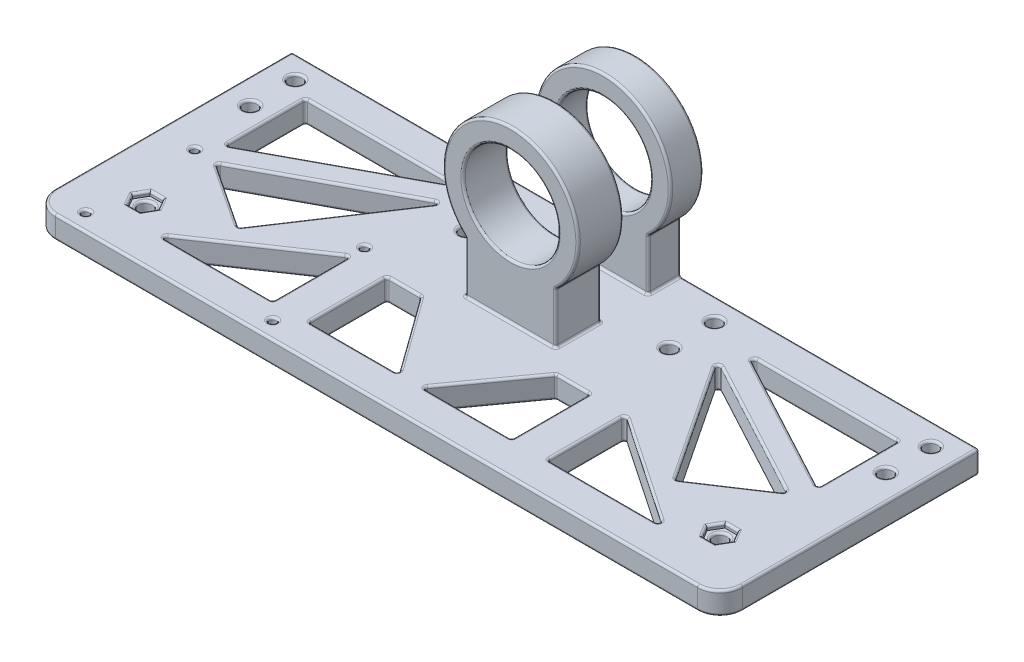
SolidWorks part; units mm, degrees
ref_plane "Front Plane" through (0, 0, 0) normal (0, 0, 1) x (1, 0, 0)
ref_plane "Top Plane" through (0, 0, 0) normal (0, 1, 0) x (1, 0, 0)
ref_plane "Right Plane" through (0, 0, 0) normal (1, 0, 0) x (0, 0, -1)
sketch "Sketch1" plane through (0, 0, 0) normal (0, 1, 0) x (1, 0, 0)
  line L0 (152.5, 115) -> (152.5, 0) construction
  line L1 (0, 0) -> (305, 0)
  line L2 (0, 0) -> (0, 115)
  line L3 (0, 115) -> (305, 115)
  line L4 (305, 0) -> (305, 115)
  line L5 (25, 90) -> (280, 90) construction
  line L6 (280, 25) -> (280, 90) construction
  line L7 (25, 25) -> (280, 25) construction
  line L8 (25, 25) -> (25, 90) construction
  line L9 (152.5, 57.5) -> (25, 57.5) construction
  line L10 (30.7735, 90) -> (27.8868, 95) construction
  line L11 (27.8868, 95) -> (22.1132, 95) construction
  line L12 (22.1132, 95) -> (19.2265, 90) construction
  line L13 (19.2265, 90) -> (22.1132, 85) construction
  line L14 (22.1132, 85) -> (27.8868, 85) construction
  line L15 (27.8868, 85) -> (30.7735, 90) construction
  line L16 (27.8868, 30) -> (30.7735, 25) construction
  line L17 (22.1132, 30) -> (27.8868, 30) construction
  line L18 (19.2265, 25) -> (22.1132, 30) construction
  line L19 (22.1132, 20) -> (19.2265, 25) construction
  line L20 (27.8868, 20) -> (22.1132, 20) construction
  line L21 (30.7735, 25) -> (27.8868, 20) construction
  line L22 (282.8868, 30) -> (277.1132, 30) construction
  line L23 (285.7735, 25) -> (282.8868, 30) construction
  line L24 (282.8868, 20) -> (285.7735, 25) construction
  line L25 (277.1132, 20) -> (282.8868, 20) construction
  line L26 (274.2265, 25) -> (277.1132, 20) construction
  line L27 (277.1132, 30) -> (274.2265, 25) construction
  line L28 (277.1132, 85) -> (274.2265, 90) construction
  line L29 (282.8868, 85) -> (277.1132, 85) construction
  line L30 (285.7735, 90) -> (282.8868, 85) construction
  line L31 (282.8868, 95) -> (285.7735, 90) construction
  line L32 (277.1132, 95) -> (282.8868, 95) construction
  line L33 (274.2265, 90) -> (277.1132, 95) construction
  line L34 (107.5, 105) -> (107.5, 115) construction
  line L35 (132.5, 0) -> (172.5, 0) construction
  line L37 (132.5, 115) -> (172.5, 115) construction
  line L41 (132.5, 25) -> (172.5, 25) construction
  line L50 (305, 14.5) -> (253.3, 14.5) construction
  line L51 (30.7735, 90) -> (22.1132, 95) construction
  line L54 (0, 115) -> (90.0836, 115) construction
  line L55 (0, 115) -> (0, 84.5) construction
  line L62 (0, 84.5) -> (0, 69.5) construction
  line L64 (62, 0) -> (62, 115) construction
  line L65 (253.3, 14.5) -> (253.3, 0) construction
  line L67 (253.3, 14.5) -> (280.2, 14.5) construction
  circle A1 centre (25, 90) radius 5 construction
  circle A3 centre (280, 25) radius 3
  circle A4 centre (25, 25) radius 3
  circle A18 centre (107.5, 105) radius 3
  circle A20 centre (107.5, 85) radius 3
  circle A23 centre (197.5, 105) radius 3
  circle A24 centre (197.5, 85) radius 3
  circle A27 centre (107.5, 65) radius 3 [skipped]
  circle A28 centre (107.5, 45) radius 3 [skipped]
  circle A29 centre (11.5, 85) radius 3
  circle A30 centre (11.5, 105) radius 3
  circle A31 centre (293.5, 105) radius 3
  circle A32 centre (293.5, 85) radius 3
  dimension "D3" = 6
  dimension "D1" = 305
  dimension "D2" = 115
  dimension "D5" = 10
  dimension "D6" = 40
  dimension "D15" = 62
  dimension "D18" = 51.7
  dimension "D19" = 14.5
  dimension "D20" = 26.9
  dimension "D8" = 20
  dimension "D9" = 45
  dimension "D11" = 11.5
  dimension "D4" = 25
  dimension "D14" = 2
  dimension "D7" = 4
  dimension "D10" = 2
extrude "Boss-Extrude1" add sketch "Sketch1" along normal blind 10
sketch "Sketch7" plane through (0, 10, 0) normal (0, 1, 0) x (1, 0, 0)
  line L0 (0, 0) -> (305, 0) construction
  line L1 (132.5, 59.5) -> (172.5, 59.5)
  line L2 (132.5, 59.5) -> (132.5, 79.5)
  line L3 (132.5, 79.5) -> (172.5, 79.5)
  line L4 (172.5, 59.5) -> (172.5, 79.5)
  line L5 (152.5, 0) -> (152.5, 115) construction
  line L6 (305, 115) -> (0, 115) construction
  line L18 (132.5, 100.5) -> (172.5, 100.5)
  line L19 (132.5, 100.5) -> (132.5, 115)
  line L20 (132.5, 115) -> (172.5, 115)
  line L21 (172.5, 100.5) -> (172.5, 115)
  point P11 (152.5, 79.5)
  point P20 (152.5, 100.5)
  dimension "D1" = 40
  dimension "D2" = 20
  dimension "D4" = 14.5
  dimension "D3" = 21
extrude "Boss-Extrude2" add sketch "Sketch7" along normal blind 22.6393
sketch "Sketch11" plane through (0, 0, -59.5) normal (0, 0, 1) x (1, 0, 0)
  circle A0 centre (152.5, 55) radius 30
  circle A1 centre (152.5, 55) radius 21.075
  dimension "D1" = 60
  dimension "D2" = 42.15
extrude "Boss-Extrude3" add sketch "Sketch11" against normal up to surface (55.5 mm away) up to face at (152.5, 13.1598, -115)
ref_plane "Plane1" through (0, 0, -57.5) normal (0, 0, 1) x (1, 0, 0)
sketch "Sketch12" plane through (305, 0, 0) normal (1, 0, 0) x (0, 0, -1)
  line L0 (115, 85) -> (59.5, 85) construction
  line L1 (79.5, 10) -> (100.5, 10)
  line L2 (79.5, 10) -> (79.5, 85)
  line L3 (79.5, 85) -> (100.5, 85)
  line L4 (100.5, 10) -> (100.5, 85)
  line L6 (100.5, 32.6393) -> (100.5, 10) construction
extrude "Cut-Extrude2" cut sketch "Sketch12" against normal through all
sketch "Sketch6" plane through (0, 10, 0) normal (0, 1, 0) x (1, 0, 0)
  line L0 (152.5, 115) -> (152.5, 0) construction
  line L8 (0, 0) -> (305, 0) construction
  line L9 (152.5, 57.5) -> (0, 57.5) construction
  line L10 (0, 115) -> (0, 0) construction
  line L29 (27.8868, 30) -> (30.7735, 25)
  line L30 (274.2265, 25) -> (277.1132, 20)
  line L31 (277.1132, 20) -> (282.8868, 20)
  line L32 (282.8868, 20) -> (285.7735, 25)
  line L33 (285.7735, 25) -> (282.8868, 30)
  line L34 (282.8868, 30) -> (277.1132, 30)
  line L35 (277.1132, 30) -> (274.2265, 25)
  line L36 (22.1132, 30) -> (27.8868, 30)
  line L37 (19.2265, 25) -> (22.1132, 30)
  line L38 (22.1132, 20) -> (19.2265, 25)
  line L39 (27.8868, 20) -> (22.1132, 20)
  line L40 (30.7735, 25) -> (27.8868, 20)
  circle A0 centre (280, 25) radius 5 construction
  dimension "D1" = 10
extrude "Cut-Extrude1" cut sketch "Sketch6" against normal blind 2
sketch "Sketch16" plane through (0, 10, 0) normal (0, 1, 0) x (1, 0, 0)
  line L0 (0, 0) -> (305, 0) construction
  line L1 (0, 115) -> (0, 0) construction
  line L2 (21, 100) -> (87.6199, 100)
  line L3 (16, 55.866) -> (107.5, 55.866) construction
  line L4 (16, 55.866) -> (16, 105) construction
  line L5 (16, 105) -> (107.5, 105) construction
  line L6 (107.5, 55.866) -> (107.5, 105) construction
  line L7 (16, 55.866) -> (107.5, 105) construction
  line L8 (16, 105) -> (107.5, 55.866) construction
  line L9 (21, 64.2262) -> (87.6199, 100)
  line L10 (21, 64.2262) -> (21, 100)
  line L11 (25.7309, 55.4161) -> (55.5519, 35.6556)
  line L12 (25.7309, 55.4161) -> (92.3508, 91.1899)
  line L13 (55.5519, 35.6556) -> (92.3508, 91.1899)
  line L14 (152.5, 115) -> (152.5, 0) construction
  line L15 (182.5, 115) -> (122.5, 115) construction
  line L16 (40.4012, 15) -> (91.45, 49.6549)
  line L17 (16, 63.8113) -> (98.95, 63.8113) construction
  line L18 (16, 63.8113) -> (16, 7.5) construction
  line L19 (16, 7.5) -> (98.95, 7.5) construction
  line L20 (98.95, 63.8113) -> (98.95, 7.5) construction
  line L21 (16, 63.8113) -> (98.95, 7.5) construction
  line L22 (16, 7.5) -> (98.95, 63.8113) construction
  line L23 (91.45, 49.6549) -> (91.45, 15)
  line L24 (40.4012, 15) -> (91.45, 15)
  line L25 (107.5, 49.6549) -> (107.5, 15)
  line L26 (107.5, 15) -> (147.5, 15)
  line L27 (147.5, 15) -> (122.5, 49.6549)
  line L28 (122.5, 49.6549) -> (107.5, 49.6549)
  line L29 (122.5, 79.5) -> (122.5, 59.5) construction
  line L30 (284, 64.2262) -> (284, 100)
  line L31 (284, 64.2262) -> (217.3801, 100)
  line L32 (284, 100) -> (217.3801, 100)
  line L33 (279.2691, 55.4161) -> (212.6492, 91.1899)
  line L34 (249.4481, 35.6556) -> (212.6492, 91.1899)
  line L35 (279.2691, 55.4161) -> (249.4481, 35.6556)
  line L36 (264.5988, 15) -> (213.55, 15)
  line L37 (213.55, 49.6549) -> (213.55, 15)
  line L38 (264.5988, 15) -> (213.55, 49.6549)
  line L39 (157.5, 15) -> (182.5, 49.6549)
  line L40 (197.5, 15) -> (157.5, 15)
  line L41 (197.5, 49.6549) -> (197.5, 15)
  line L42 (182.5, 49.6549) -> (197.5, 49.6549)
  circle A0 centre (16, 7.5) radius 1.55
  circle A1 centre (98.95, 7.5) radius 1.55
  circle A2 centre (16, 55.866) radius 1.55
  circle A3 centre (91.33, 55.866) radius 1.55
  point P10 (61.75, 80.433)
  point P18 (57.475, 35.6556)
  dimension "D1" = 3.1
  dimension "D2" = 7.5
  dimension "D3" = 82.95
  dimension "D4" = 16
  dimension "D5" = 48.366
  dimension "D6" = 75.33
  dimension "D7" = 5
  dimension "D8" = 7.5
  dimension "D9" = 5
extrude "Cut-Extrude3" cut sketch "Sketch16" against normal through all
fillet "Fillet3" radius 10 2 edges at (305, 5, 0) (0, 5, 0)
chamfer "Chamfer2" distance 1.65 4 edges at (98.95, 0, -5.95) (91.33, 0, -54.316) (16, 0, -5.95) (16, 0, -54.316)
fillet "Fillet5" radius 1 156 edges at (54.31, 0, -82.1131) (73.9513, 0, -63.4227) (91.45, 0, -32.3275) (135, 0, -32.3275) (197.5, 0, -32.3275) (239.0744, 0, -15) (284, 0, -82.1131) (264.3586, 0, -45.5358) (0, 0, -62.5) (2.9289, 0, -2.9289) (152.5, 0, 0) (302.0711, 0, -2.9289) (293.5, 0, -108) (293.5, 0, -88) (197.5, 0, -108) (197.5, 0, -88) (280, 8, -22) (280, 0, -22) (107.5, 0, -102) (107.5, 0, -82) (25, 0, -28) (25, 8, -28) (11.5, 0, -102) (11.5, 0, -82) (21, 0, -82.1131) (21, 5, -64.2262) (40.6414, 0, -45.5358) (55.5519, 5, -35.6556) (65.9256, 0, -15) (91.45, 5, -15) (87.6199, 5, -100) (54.31, 0, -100) (21, 5, -100) (92.3508, 5, -91.1899) (59.0409, 0, -73.303) (25.7309, 5, -55.4161) (91.45, 5, -49.6549) (65.9256, 0, -32.3275) (40.4012, 5, -15) (107.5, 0, -32.3275) (122.5, 5, -49.6549) (115, 0, -49.6549) (107.5, 5, -49.6549) (107.5, 5, -15) (127.5, 0, -15) (147.5, 5, -15) (177.5, 0, -15) (197.5, 5, -15) (197.5, 5, -49.6549) (190, 0, -49.6549) (182.5, 5, -49.6549) (170, 0, -32.3275) (157.5, 5, -15) (264.5988, 5, -15) (239.0744, 0, -32.3275) (213.55, 5, -49.6549) (213.55, 0, -32.3275) (213.55, 5, -15) (284, 5, -100) (250.69, 0, -100) (217.3801, 5, -100) (250.69, 0, -82.1131) (284, 5, -64.2262) (279.2691, 5, -55.4161) (245.9591, 0, -73.303) (212.6492, 5, -91.1899) (231.0487, 0, -63.4227) (249.4481, 5, -35.6556) (305, 0, -62.5) (131.425, 55, -100.5) (132.5, 21.3197, -100.5) (172.5, 21.3197, -100.5) (173.575, 55, -115) (0, 5, -115) (152.5, 0, -115) (305, 5, -115) (172.5, 21.3197, -115) (132.5, 21.3197, -115) (132.5, 32.6393, -107.75) (152.5, 85, -115) (172.5, 32.6393, -107.75) (152.5, 85, -100.5) (173.575, 55, -79.5) (172.5, 21.3197, -79.5) (152.5, 85, -79.5) (172.5, 32.6393, -69.5) (132.5, 21.3197, -79.5) (132.5, 32.6393, -69.5) (173.575, 55, -59.5) (132.5, 21.3197, -59.5) (152.5, 85, -59.5) (172.5, 21.3197, -59.5) (107.5, 10, -102) (11.5, 10, -102) (107.5, 10, -82) (197.5, 10, -88) (11.5, 10, -82) (293.5, 10, -88) (2.9289, 10, -2.9289) (0, 10, -62.5) (66.25, 10, -115) (132.5, 10, -107.75) (152.5, 10, -100.5) (172.5, 10, -107.75) (238.75, 10, -115) (305, 10, -62.5) (302.0711, 10, -2.9289) (152.5, 10, 0) (293.5, 10, -108) (197.5, 10, -108) (132.5, 10, -69.5) (152.5, 10, -59.5) (172.5, 10, -69.5) (152.5, 10, -79.5) (280, 10, -20) (284.3301, 10, -22.5) (284.3301, 10, -27.5) (280, 10, -30) (275.6699, 10, -27.5) (275.6699, 10, -22.5) (20.6699, 10, -22.5) (25, 10, -20) (29.3301, 10, -22.5) (29.3301, 10, -27.5) (25, 10, -30) (20.6699, 10, -27.5) (127.5, 10, -15) (135, 10, -32.3275) (115, 10, -49.6549) (107.5, 10, -32.3275) (231.0487, 10, -63.4227) (264.3586, 10, -45.5358) (245.9591, 10, -73.303) (190, 10, -49.6549) (170, 10, -32.3275) (177.5, 10, -15) (197.5, 10, -32.3275) (239.0744, 10, -15) (239.0744, 10, -32.3275) (213.55, 10, -32.3275) (16, 10, -5.95) (98.95, 10, -5.95) (54.31, 10, -100) (21, 10, -82.1131) (54.31, 10, -82.1131) (16, 10, -54.316) (284, 10, -82.1131) (250.69, 10, -100) (250.69, 10, -82.1131) (65.9256, 10, -32.3275) (65.9256, 10, -15) (91.45, 10, -32.3275) (91.33, 10, -54.316) (40.6414, 10, -45.5358) (73.9513, 10, -63.4227) (59.0409, 10, -73.303)
equation "\"joint_width\"=4"
equation "\"short_base_length\"=11.5"
equation "\"D2@Sketch1\"=\"short_base_length\""
equation "\"outer_diam_main_joint\"=6"
equation "\"D1@Sketch11\"=\"outer_diam_main_joint\""
equation "\"D1@Sketch7\"=\"outer_diam_main_joint\"-2"
equation "\"D1@Boss-Extrude2\"=(\"outer_diam_main_joint\"/2)+1.5cm-sqr((\"outer_diam_main_joint\"/2)^2-((\"outer_diam_main_joint\"-2)/2)^2)"
equation "\"D6@Sketch1\"=\"outer_diam_main_joint\"-2"
equation "\"pulleyside\"=1.5"
